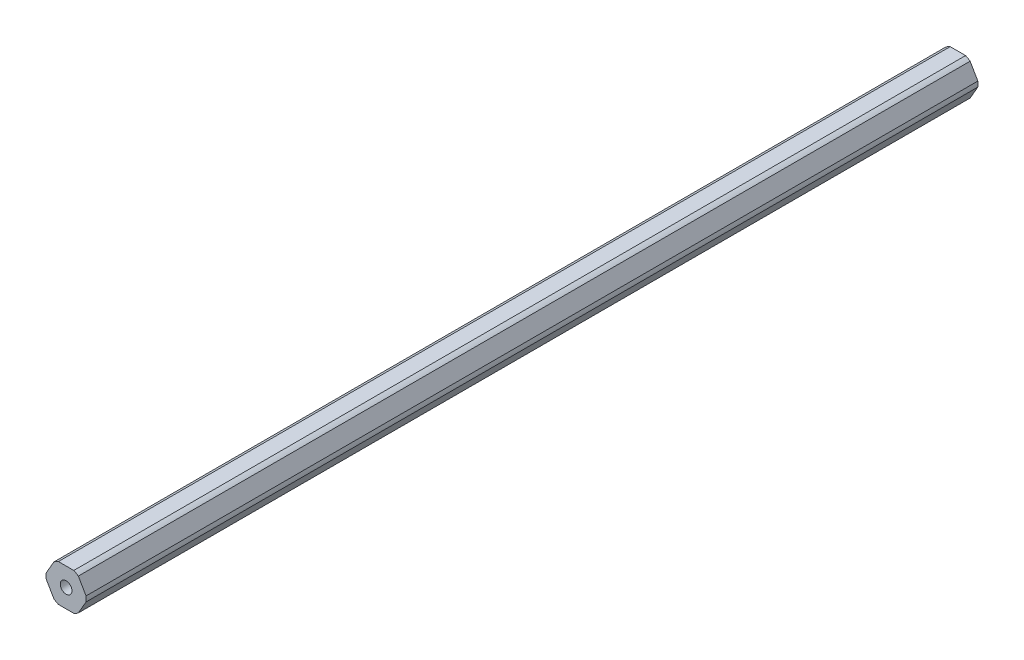
SolidWorks part; units mm, degrees
material "6061-T6 (SS)"
ref_plane "Front Plane" through (0, 0, 0) normal (0, 0, 1) x (1, 0, 0)
ref_plane "Top Plane" through (0, 0, 0) normal (0, 1, 0) x (1, 0, 0)
ref_plane "Right Plane" through (0, 0, 0) normal (1, 0, 0) x (0, 0, -1)
sketch "Sketch1" plane through (0, 0, 0) normal (0, 0, 1) x (1, 0, 0)
  line L1 (3.6662, 6.35) -> (-3.6662, 6.35)
  line L2 (-3.6662, 6.35) -> (-7.3323, 0)
  line L3 (-7.3323, 0) -> (-3.6662, -6.35)
  line L4 (-3.6662, -6.35) -> (3.6662, -6.35)
  line L5 (3.6662, -6.35) -> (7.3323, 0)
  line L6 (7.3323, 0) -> (3.6662, 6.35)
  circle A0 centre (0, 0) radius 6.35 construction
  circle A1 centre (0, 0) radius 2
  circle A2 centre (0, 0) radius 6.875
  point P1 (0, 6.35)
  dimension "D2" = 13.75
  dimension "D3" = 4
  dimension "D1" = 12.7
extrude "Boss-Extrude1" add sketch "Sketch1" along normal mid plane 304.8 contours L6 A2 L1 L2 L3 L4 L5 A1 region at (3.3439, 5.7918, 0)
sketch "Sketch4" plane through (0, 0, 152.4) normal (0, 0, 1) x (1, 0, 0)
  circle A0 centre (0, 0) radius 6.35
  circle A2 centre (0, 0) radius 2.4892
  dimension "D1" = 12.7
  dimension "D2" = 4.9784
equation "\"D2@Sketch1\"=13.75mm"
equation "\"D3@Sketch1\"=4mm"
